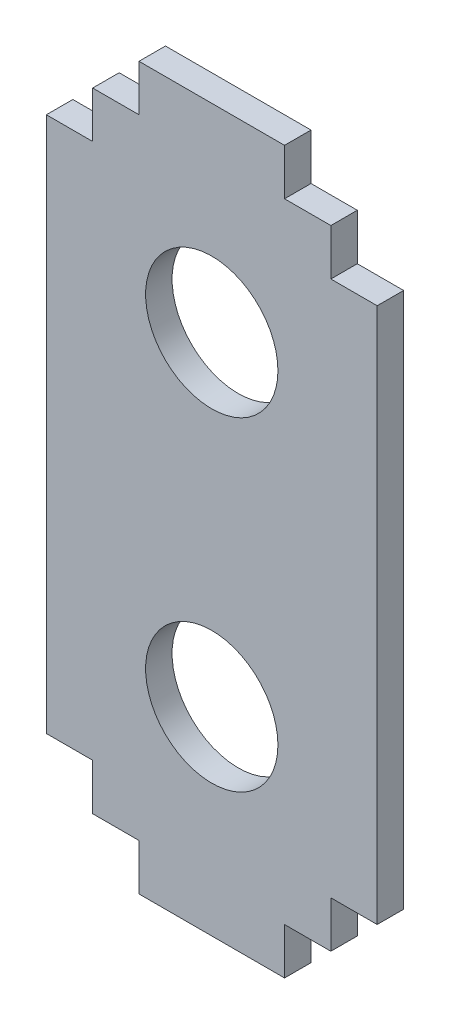
SolidWorks part; units mm, degrees
material "СТ3КП"
ref_plane "Спереди" through (0, 0, 0) normal (0, 0, 1) x (1, 0, 0)
ref_plane "Сверху" through (0, 0, 0) normal (0, 1, 0) x (1, 0, 0)
ref_plane "Справа" through (0, 0, 0) normal (1, 0, 0) x (0, 0, -1)
sketch "Эскиз1" plane through (0, 0, 0) normal (0, 0, 1) x (1, 0, 0)
  line L0 (-25, 0) -> (25, 0) construction
  line L1 (0, -1000) -> (0, 49000) construction
  line L2 (-25, 16) -> (-25, -65)
  line L3 (-25, 16) -> (-18, 16)
  line L4 (-18, 16) -> (-18, 23)
  line L5 (-18, 23) -> (-11, 23)
  line L6 (-11, 23) -> (-11, 30)
  line L7 (-11, 30) -> (11, 30)
  line L8 (-1002.9143, -24.5) -> (48997.0857, -24.5) construction
  line L9 (-11, -72) -> (-11, -79)
  line L10 (-11, -79) -> (11, -79)
  line L11 (-18, -72) -> (-11, -72)
  line L12 (-18, -65) -> (-18, -72)
  line L13 (-25, -65) -> (-18, -65)
  line L14 (11, -72) -> (11, -79)
  line L15 (18, -72) -> (11, -72)
  line L16 (18, -65) -> (18, -72)
  line L17 (25, -65) -> (18, -65)
  line L18 (25, 16) -> (25, -65)
  line L19 (25, 16) -> (18, 16)
  line L20 (18, 16) -> (18, 23)
  line L21 (18, 23) -> (11, 23)
  line L22 (11, 23) -> (11, 30)
  circle A0 centre (0, 0) radius 10
  circle A1 centre (0, -49) radius 10
  point P5 (0, 0)
  point P25 (0, 0)
  point P26 (0, -79)
  point P35 (0, 30)
  dimension "D1" = 20
  dimension "D2" = 29
  dimension "D3" = 50
  dimension "D4" = 6
  dimension "D5" = 7
base flange "Базовая кромка1" sketch "Эскиз1" thickness 4 reverse thickness direction no parameters "D1"=1.5
sketch "Сгиб-Линии1" [suppressed] plane through (0, 0, 0) normal (0, 1, 0) x (1, 0, 0)
sketch "Граничная рамка1" [suppressed] plane through (0, 0, 0) normal (0, 1, 0) x (1, 0, 0)
sheet metal parameters "Листовой металл3" thickness 4 parameters "D1"=1.5
flat pattern "Развертка3" [suppressed]
sketch "Сгиб-Линии2" plane through (0, 0, 0) normal (0, 1, 0) x (1, 0, 0)
sketch3d "Граничная рамка2" [suppressed]
  line L0 (25, 30, 0) -> (25, -79, 0) construction
  line L1 (-25, 30, 0) -> (-25, -79, 0) construction
  line L2 (25, 30, 0) -> (-25, 30, 0) construction
  line L3 (25, -79, 0) -> (-25, -79, 0) construction
